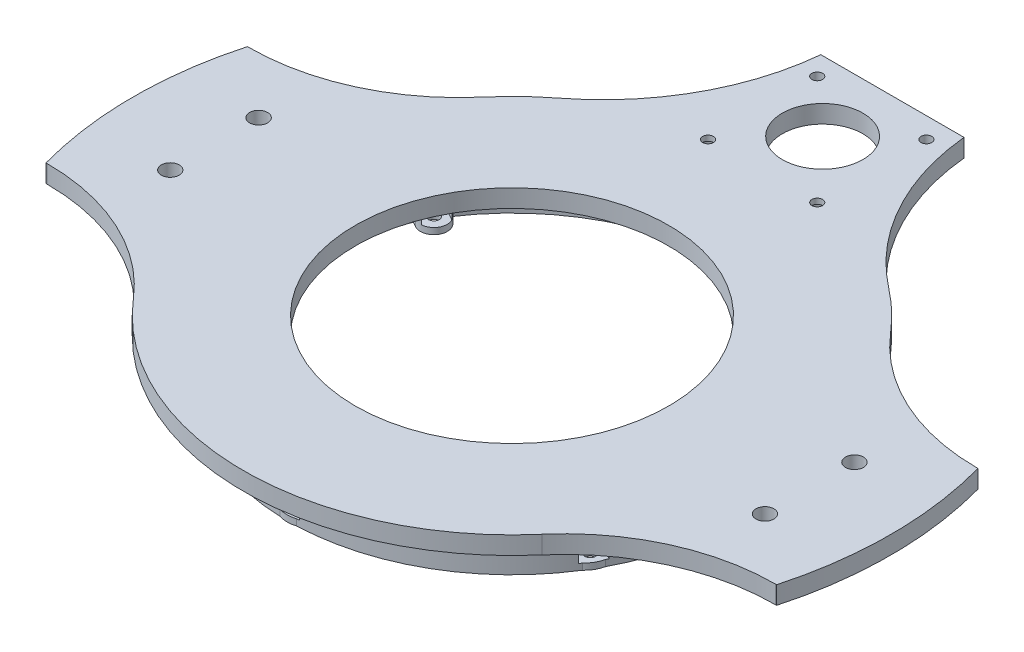
SolidWorks part; units mm, degrees
material "ABS"
ref_plane "Front Plane" through (0, 0, 0) normal (0, 0, 1) x (1, 0, 0)
ref_plane "Top Plane" through (0, 0, 0) normal (0, 1, 0) x (1, 0, 0)
ref_plane "Right Plane" through (0, 0, 0) normal (1, 0, 0) x (0, 0, -1)
sketch "Sketch1" plane through (0, 0, 0) normal (0, 1, 0) x (1, 0, 0)
  circle A0 centre (0, 0) radius 76.2
  circle A1 centre (0, 0) radius 44.45
  dimension "D1" = 152.4
  dimension "D2" = 88.9
extrude "Boss-Extrude1" add sketch "Sketch1" along normal blind 5.08
sketch "Sketch6" plane through (0, 5.08, 0) normal (0, 1, 0) x (1, 0, 0)
  line L1 (-103.6593, 28.575) -> (-70.6393, 28.575)
  line L2 (-103.6593, -28.575) -> (-70.6393, -28.575)
  line L3 (0, 0) -> (0, 24.6731) construction
  line L4 (103.6593, -28.575) -> (70.6393, -28.575)
  line L6 (103.6593, 28.575) -> (70.6393, 28.575)
  circle A0 centre (0, 0) radius 76.2 construction
  arc A1 (-70.6393, 28.575) -> (-70.6393, -28.575) centre (0, 0) ccw
  arc A2 (70.6393, -28.575) -> (70.6393, 28.575) centre (0, 0) ccw
  arc A3 (-103.6593, 28.575) -> (-103.6593, -28.575) centre (0, 0) ccw
  arc A4 (103.6593, -28.575) -> (103.6593, 28.575) centre (0, 0) ccw
  point P3 (-103.6593, 0)
  dimension "D1" = 33.02
  dimension "D2" = 57.15
  dimension "D3" = 33.02
extrude "Boss-Extrude12" add sketch "Sketch6" against normal through all
sketch "Sketch7" plane through (0, 5.08, 0) normal (0, 1, 0) x (1, 0, 0)
  line L0 (-103.6593, 28.575) -> (-103.3217, 28.575)
  line L1 (-103.6593, 28.575) -> (-103.6593, -28.575)
  line L2 (-103.6593, -28.575) -> (-103.3217, -28.575)
  line L4 (103.3217, -28.575) -> (103.6593, -28.575)
  line L5 (103.6593, -28.575) -> (103.6593, 28.575)
  line L6 (103.6593, 28.575) -> (103.3217, 28.575)
  arc A0 (-57.9374, -49.4944) -> (57.9374, -49.4944) centre (0, 0) ccw
  arc A1 (57.9374, 49.4944) -> (-57.9374, 49.4944) centre (0, 0) ccw
  arc A2 (103.3217, 28.575) -> (57.9374, 49.4944) centre (103.3217, 88.265) cw
  arc A3 (57.9374, -49.4944) -> (103.3217, -28.575) centre (103.3217, -88.265) cw
  arc A4 (-103.3217, -28.575) -> (-57.9374, -49.4944) centre (-103.3217, -88.265) cw
  arc A5 (-103.3217, 28.575) -> (-57.9374, 49.4944) centre (-103.3217, 88.265) ccw
  circle A6 centre (0, 0) radius 44.45
  point P20 (70.6393, 28.575)
  point P23 (70.6393, -28.575)
  point P26 (-70.6393, -28.575)
  point P29 (-70.6393, 28.575)
  dimension "D1" = 59.69
extrude "Boss-Extrude13" add sketch "Sketch7" against normal through all
sketch "Sketch8" plane through (0, 5.08, 0) normal (0, 1, 0) x (1, 0, 0)
  circle A1 centre (-84.6093, 12.7) radius 2.54
  circle A2 centre (-84.2717, -12.7) radius 2.54
  circle A3 centre (84.6093, 12.573) radius 2.54
  circle A4 centre (84.6093, -12.827) radius 2.54
  dimension "D2" = 15.875
  dimension "D3" = 25.4
  dimension "D4" = 19.05
  dimension "D5" = 5.08
  dimension "D6" = 5.08
  dimension "D7" = 5.08
  dimension ".20" = 5.08
  dimension "D8" = 25.4
  dimension "D9" = 16.002
  dimension "D10" = 19.05
  dimension "D1" = 19.05
extrude "Cut-Extrude1" cut sketch "Sketch8" against normal through all
sketch "Sketch11" plane through (0, 0, 0) normal (0, -1, 0) x (1, 0, 0)
  circle A0 centre (84.6093, -12.573) radius 2.5577
  circle A1 centre (84.6093, 12.827) radius 2.4439
  circle A2 centre (-84.2717, 12.7) radius 2.4457
  circle A3 centre (-84.6093, -12.7) radius 2.5634
extrude "Cut-Extrude2" cut sketch "Sketch11" against normal through all
sketch "Sketch12" plane through (0, 0, 0) normal (0, -1, 0) x (1, 0, 0)
  circle A0 centre (0, 0) radius 63.5
  circle A1 centre (0, 0) radius 62.23
  dimension "D1" = 127
  dimension "D2" = 124.46
extrude "Boss-Extrude15" add sketch "Sketch12" along normal blind 13.716
sketch "Sketch13" plane through (0, 0, 0) normal (0, -1, 0) x (1, 0, 0)
  circle A0 centre (0, 0) radius 63.5
  circle A1 centre (0, 0) radius 66.04
  dimension "D1" = 2.54
extrude "Boss-Extrude16" add sketch "Sketch13" along normal blind 3.81
sketch "Sketch14" plane through (0, 0, 0) normal (0, -1, 0) x (1, 0, 0)
  line L1 (20.32, -64.77) -> (-20.32, -64.77)
  line L2 (20.32, -64.77) -> (20.32, -107.95)
  line L3 (20.32, -107.95) -> (-20.32, -107.95)
  line L4 (-20.32, -64.77) -> (-20.32, -107.95)
  circle A2 centre (0, -88.138) radius 11.43
  dimension "D3" = 22.86
  dimension "D4" = 23.368
  dimension "D5" = 20.32
  dimension "D6" = 64.77
  dimension "D1" = 43.18
  dimension "D2" = 40.64
extrude "Boss-Extrude17" add sketch "Sketch14" against normal blind 5.08
sketch "Sketch15" plane through (0, 5.08, 0) normal (0, 1, 0) x (1, 0, 0)
  line L0 (-20.32, 107.95) -> (20.32, 107.95) construction
  line L1 (20.32, 107.95) -> (20.32, 73.4407) construction
  circle A0 centre (0, 88.138) radius 11.43
  circle A1 centre (-15.494, 102.108) radius 1.524
  circle A2 centre (15.494, 102.108) radius 1.524
  circle A3 centre (15.494, 71.12) radius 1.524
  circle A4 centre (-15.494, 71.12) radius 1.524
  dimension "D1" = 3.048
  dimension "D2" = 3.048
  dimension "D3" = 3.048
  dimension "D4" = 3.048
  dimension "D5" = 30.988
  dimension "D6" = 30.988
  dimension "D7" = 5.842
  dimension "D8" = 5.842
  dimension "D9" = 30.988
  dimension "D10" = 30.988
  dimension "D11" = 4.826
  dimension "D12" = 4.826
  dimension "D13" = 22.86
extrude "Cut-Extrude3" cut sketch "Sketch15" against normal blind 5.08
sketch "Sketch17" plane through (0, 0, 0) normal (0, -1, 0) x (1, 0, 0)
  arc A0 (53.7684, -33.7818) -> (56.1401, -29.6739) centre (0, 0) ccw
  arc A1 (2.3717, -63.4557) -> (-2.3717, -63.4557) centre (0, -55.88) cw
  arc A2 (-53.7684, -33.7818) -> (-56.1401, -29.6739) centre (-48.3935, -27.94) cw
  circle A3 centre (0, 0) radius 63.5 construction
  arc A4 (-56.1401, 29.6739) -> (-53.7684, 33.7818) centre (-48.3935, 27.94) cw
  arc A5 (-2.3717, 63.4557) -> (2.3717, 63.4557) centre (0, 55.88) cw
  arc A6 (53.7684, 33.7818) -> (56.1401, 29.6739) centre (48.3935, 27.94) cw
  arc A7 (56.1401, -29.6739) -> (53.7684, -33.7818) centre (48.3935, -27.94) cw
  arc A8 (-2.3717, -63.4557) -> (2.3717, -63.4557) centre (0, 0) ccw
  arc A9 (-56.1401, -29.6739) -> (-53.7684, -33.7818) centre (0, 0) ccw
  arc A10 (-53.7684, 33.7818) -> (-56.1401, 29.6739) centre (0, 0) ccw
  arc A11 (2.3717, 63.4557) -> (-2.3717, 63.4557) centre (0, 0) ccw
  arc A12 (56.1401, 29.6739) -> (53.7684, 33.7818) centre (0, 0) ccw
  point P26 (0, 0)
  dimension "D1" = 55.88
  dimension "D2" = 127
  dimension "D4" = 127
  dimension "D3" = 6
extrude "Boss-Extrude19" add sketch "Sketch17" along normal through all
sketch "Sketch18" plane through (0, 0, 0) normal (0, -1, 0) x (1, 0, 0)
  line L0 (-3.81, -60.579) -> (-3.81, -62.1133)
  line L1 (3.81, -60.579) -> (3.81, -62.1133)
  line L2 (-54.368, -26.9899) -> (-55.6967, -27.7571)
  line L3 (-50.558, -33.5891) -> (-51.8867, -34.3562)
  line L4 (-50.558, 33.5891) -> (-51.8867, 34.3562)
  line L5 (-54.368, 26.9899) -> (-55.6967, 27.7571)
  line L6 (3.81, 60.579) -> (3.81, 62.1133)
  line L7 (-3.81, 60.579) -> (-3.81, 62.1133)
  line L8 (54.368, 26.9899) -> (55.6967, 27.7571)
  line L9 (50.558, 33.5891) -> (51.8867, 34.3562)
  line L10 (50.558, -33.5891) -> (51.8867, -34.3562)
  line L11 (54.368, -26.9899) -> (55.6967, -27.7571)
  arc A1 (3.81, -60.579) -> (-3.81, -60.579) centre (0, -60.579) ccw
  circle A7 centre (0, -60.579) radius 1.524
  circle A15 centre (-52.463, -30.2895) radius 1.524
  arc A16 (-50.558, -33.5891) -> (-54.368, -26.9899) centre (-52.463, -30.2895) ccw
  circle A18 centre (-52.463, 30.2895) radius 1.524
  arc A19 (-54.368, 26.9899) -> (-50.558, 33.5891) centre (-52.463, 30.2895) ccw
  circle A21 centre (0, 60.579) radius 1.524
  arc A22 (-3.81, 60.579) -> (3.81, 60.579) centre (0, 60.579) ccw
  circle A24 centre (52.463, 30.2895) radius 1.524
  arc A25 (50.558, 33.5891) -> (54.368, 26.9899) centre (52.463, 30.2895) ccw
  circle A27 centre (52.463, -30.2895) radius 1.524
  arc A28 (54.368, -26.9899) -> (50.558, -33.5891) centre (52.463, -30.2895) ccw
  circle A29 centre (0, 0) radius 62.23 construction
  arc A30 (51.8867, -34.3562) -> (55.6967, -27.7571) centre (0, 0) ccw
  arc A31 (-3.81, -62.1133) -> (3.81, -62.1133) centre (0, 0) ccw
  arc A32 (-55.6967, -27.7571) -> (-51.8867, -34.3562) centre (0, 0) ccw
  arc A33 (55.6967, 27.7571) -> (51.8867, 34.3562) centre (0, 0) ccw
  arc A34 (-51.8867, 34.3562) -> (-55.6967, 27.7571) centre (0, 0) ccw
  arc A35 (3.81, 62.1133) -> (-3.81, 62.1133) centre (0, 0) ccw
  point P17 (0, 0)
  point P29 (0, 0)
  point P42 (0, 0)
  dimension "D2" = 7.62
  dimension "D3" = 3.048
  dimension "D4" = 60.579
other "Pen Sketch1" parameters "D2"=11.8597, "D3"=2.2491, "D5"=6, "D4"=124.46, "D1"=6
extrude "Boss-Extrude20" add sketch "Sketch18" along normal through all
ref_plane "Plane1" through (0, 0, -62.1133) normal (0, 0, 1) x (1, 0, 0)
sketch "Sketch19" plane through (0, 0, -62.1133) normal (0, 0, 1) x (1, 0, 0)
  line L0 (-3.81, -13.716) -> (3.81, -13.716) construction
  line L1 (3.175, -11.938) -> (-3.175, -11.938)
  line L2 (3.175, -11.938) -> (3.175, -9.144)
  line L3 (3.175, -9.144) -> (-3.175, -9.144)
  line L4 (-3.175, -11.938) -> (-3.175, -9.144)
  line L5 (3.81, -13.716) -> (3.81, 0) construction
  dimension "D1" = 2.794
  dimension "D2" = 6.35
  dimension "D3" = 1.778
  dimension "D4" = 0.635
extrude "Cut-Extrude4" cut sketch "Sketch19" along normal blind 15.24 and the other way blind 15.24
pattern_circular "CirPattern1" count 6 over 360 about axis through (0, 0, 0) along (0, 1, 0) of "Cut-Extrude4"
sketch "Sketch21" plane through (0, 0, 0) normal (0, -1, 0) x (1, 0, 0)
  circle A0 centre (15.494, -71.12) radius 3.048
  circle A1 centre (-15.494, -71.12) radius 3.048
  dimension "D1" = 6.096
  dimension "D2" = 6.096
extrude "Cut-Extrude6" cut sketch "Sketch21" against normal blind 3.556
fillet "Fillet2" radius 68.58 2 edges at (20.32, 2.54, -73.4407) (-20.32, 2.54, -73.4407)
